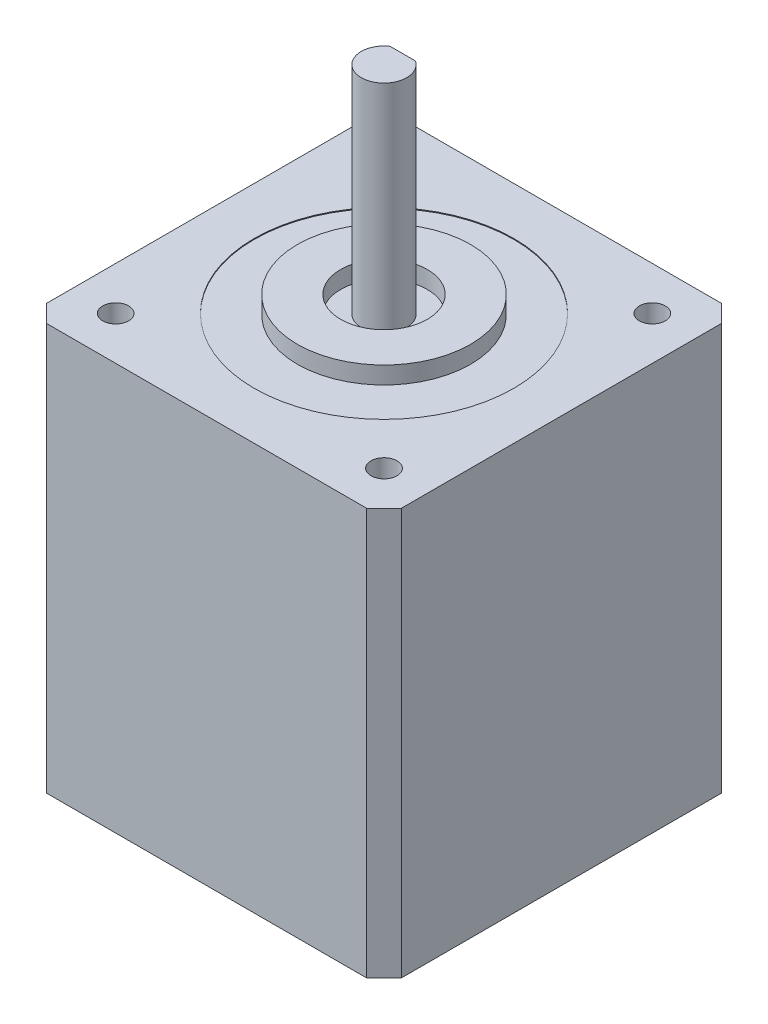
SolidWorks part; units mm, degrees
ref_plane "Front Plane" through (0, 0, 0) normal (0, 0, 1) x (1, 0, 0)
ref_plane "Top Plane" through (0, 0, 0) normal (0, 1, 0) x (1, 0, 0)
ref_plane "Right Plane" through (0, 0, 0) normal (1, 0, 0) x (0, 0, -1)
sketch "Sketch1" plane through (0, 0, 0) normal (0, 1, 0) x (1, 0, 0)
  line L0 (-20.5, 18.5) -> (-18.5, 20.5)
  line L1 (-18.5, -20.5) -> (18.5, -20.5)
  line L2 (-20.5, -18.5) -> (-20.5, 18.5)
  line L3 (-18.5, 20.5) -> (18.5, 20.5)
  line L4 (20.5, -18.5) -> (20.5, 18.5)
  line L5 (-20.5, -20.5) -> (20.5, 20.5) construction
  line L6 (-20.5, 20.5) -> (20.5, -20.5) construction
  line L7 (-18.5, -20.5) -> (-20.5, -18.5)
  line L8 (18.5, -20.5) -> (20.5, -18.5)
  line L9 (20.5, 18.5) -> (18.5, 20.5)
  point P0 (0, 0)
  dimension "D1" = 41
  dimension "D2" = 41
extrude "Boss-Extrude1" add sketch "Sketch1" along normal blind 47
sketch "Sketch2" plane through (0, 47, 0) normal (0, 1, 0) x (-1, 0, 0)
  circle A0 centre (0, 0) radius 15
extrude "Cut-Extrude1" cut sketch "Sketch2" against normal blind 0.1
sketch "Sketch3" plane through (0, 46.9, 0) normal (0, 1, 0) x (1, 0, 0)
  circle A0 centre (0, 0) radius 10
  circle A1 centre (0, 0) radius 5
extrude "Boss-Extrude2" add sketch "Sketch3" along normal blind 2
sketch "Sketch4" plane through (0, 46.9, 0) normal (0, 1, 0) x (1, 0, 0)
  line L0 (-1.471, 2.1754) -> (1.471, 2.1754)
  arc A0 (-1.471, 2.1754) -> (1.471, 2.1754) centre (0, 0) ccw
extrude "Boss-Extrude3" add sketch "Sketch4" along normal blind 25
hole_wizard "Ø3.0 (3) Diameter Hole1" positions "Sketch6" profile "Sketch5" hole size "Ø3.0" standard "Ansi Metric"
sketch "Sketch6" plane through (0, 47, 0) normal (0, 1, 0) x (-1, 0, 0)
  arc A0 (1.471, -2.1754) -> (-1.471, -2.1754) centre (0, 0) ccw construction
  point P0 (-15.5, -15.5)
  point P1 (15.5, -15.5)
  point P3 (15.5, 15.5)
  point P5 (-15.5, 15.5)
  dimension "D3" = 15.5
  dimension "D1" = 31
  dimension "D2" = 31
  dimension "D4" = 15.5
sketch "Sketch5" plane through (15.5, 47, -15.5) normal (1, 0, 0) x (0, 0, 1)
  line L0 (0, 0) -> (0, 5.9013)
  line L1 (0, 5.9013) -> (1.5, 5)
  line L2 (1.5, 5) -> (1.5, 0)
  line L5 (1.5, 0) -> (0, 0)
  line L10 (0, 5.9013) -> (-1.5, 5) construction
  line L11 (0, -6.35) -> (0, 107.95) construction
  dimension "Hole Dia." = 3
  dimension "Hole Depth" = 5
  dimension "Drill Angle" = 118
ref_axis "Motor Axis" through (0, 71.9, 0) along (0, -1, 0)
